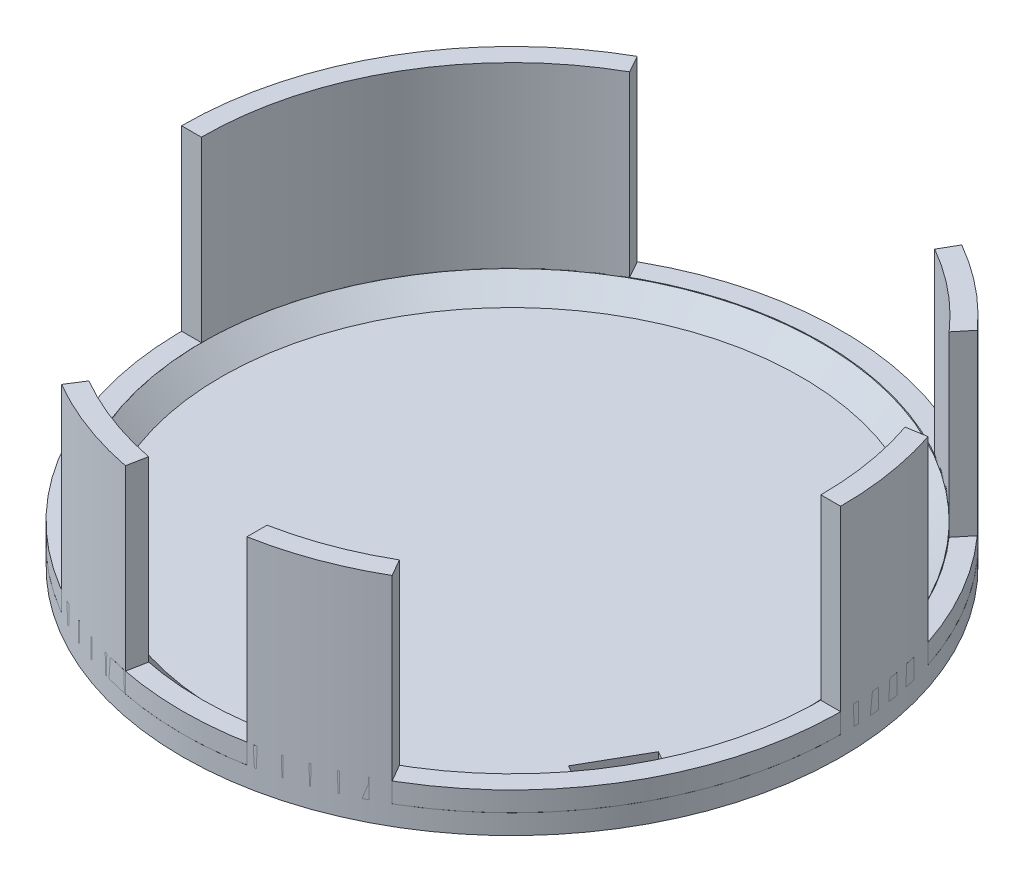
SolidWorks part; units mm, degrees
ref_plane "Front Plane" through (0, 0, 0) normal (0, 0, 1) x (1, 0, 0)
ref_plane "Top Plane" through (0, 0, 0) normal (0, 1, 0) x (1, 0, 0)
ref_plane "Right Plane" through (0, 0, 0) normal (1, 0, 0) x (0, 0, -1)
sketch "Sketch1" plane through (0, 0, 0) normal (0, 1, 0) x (1, 0, 0)
  circle A0 centre (0, 0) radius 25
extrude "Boss-Extrude1" add sketch "Sketch1" along normal blind 1.5
sketch "Sketch3" plane through (0, 1.5, 0) normal (0, 1, 0) x (1, 0, 0)
  line L0 (0, 0) -> (-16.5621, -18.7269)
  circle A0 centre (0, 0) radius 25 construction
  circle A1 centre (0, 0) radius 25
  circle A2 centre (0, 0) radius 23.5
extrude "Boss-Extrude2" add sketch "Sketch3" along normal blind 15 contours A2 A1 region at (-9.9796, 1.5, -22.1484)
sketch "Sketch4" plane through (0, 1.5, 0) normal (0, 1, 0) x (1, 0, 0)
  line L12 (12.5369, -21.6293) -> (11.7268, -20.2317)
  line L13 (-12.5582, -21.6169) -> (-11.692, -20.2518)
  line L14 (23.3845, -0.0671) -> (24.9999, -0.0671)
  line L15 (11.6192, 20.2937) -> (12.4219, 21.6955)
  line L16 (-11.4849, 20.37) -> (-12.2782, 21.7772)
  line L17 (-23.3845, -0.0671) -> (-24.9999, -0.0671)
  line L18 (4.4842, -24.5945) -> (4.4842, -22.9506)
  line L20 (-4.4866, -22.9501) -> (-4.7966, -24.5355)
  line L21 (22.1294, 7.5584) -> (23.7437, 7.8254)
  line L23 (17.5844, 15.4152) -> (18.6211, 16.681)
  circle A1 centre (0, 0) radius 23.3846
  circle A2 centre (0, 0) radius 25
  circle M13 centre (0, 0) radius 23.5
extrude "Cut-Extrude3" cut sketch "Sketch4" against normal blind 0.001 and the other way blind 15 contours L12 A2 L14 M13 | L20 A2 L18 M13 | L21 A2 L23 M13 | L15 A2 L16 M13 | L17 A2 L13 M13 region at (12.3796, 1.5, 20.8536) region at (-0.0856, 1.5, 24.1088) region at (-21.4316, 1.5, 12.3735) region at (20.8613, 1.5, -12.0676) region at (0.0818, 1.5, -24.7486)
sketch "Sketch5" plane through (0, 0, 0) normal (0, -1, 0) x (1, 0, 0)
  line L0 (0, 0) -> (18.8419, 10.7717)
  line L1 (12.6838, 21.5435) -> (25, 0)
  line L2 (18.8419, 10.7717) -> (21.7036, 12.4078)
  line L3 (18.8419, 10.7717) -> (17.6008, 12.9427)
  line L8 (17.6008, 12.9427) -> (18.4777, 13.444)
  line L9 (18.4777, 13.444) -> (20.9605, 9.1011)
  line L10 (20.9605, 9.1011) -> (19.2165, 8.1041)
  line L11 (19.2165, 8.1041) -> (16.7337, 12.447)
  line L12 (16.7337, 12.447) -> (17.6008, 12.9427)
  line L13 (55.1315, -18.0689) -> (16.7337, -26.7785)
  circle A0 centre (0, 0) radius 25 construction
extrude "Cut-Extrude4" cut sketch "Sketch5" against normal blind 5.001 contours L12 L11 L0 L1 | L9 L8 L1 L2 | L10 L9 L2 L1 | L11 L10 L1 L0 region at (17.7878, 0, 11.6094) region at (19.0292, 0, 9.4379) region at (19.9012, 0, 9.9364) region at (18.6598, 0, 12.1079)
sketch "Sketch8" plane through (0, 0, 0.0671) normal (0, 0, 1) x (1, 0, 0)
  line L0 (-23.4999, 1.5) -> (-23.4999, 3)
  line L1 (-23.4999, 1.5) -> (-23.4999, 16.5) construction
  line L2 (-23.4999, 1.5) -> (-21.9999, 1.5)
  line L3 (-23.4999, 3) -> (-21.9999, 1.5)
  line L4 (0, 0) -> (0, 7.9293)
revolve "Revolve4" add sketch "Sketch8" angle 360 about L4 region at (-22.9999, 2, 0.0671)
sketch "Sketch9" plane through (0, 1.5, 0) normal (0, 1, 0) x (1, 0, 0)
  circle A0 centre (0, 0) radius 23.5
  circle A1 centre (0, 0) radius 25
extrude "Boss-Extrude4" add sketch "Sketch9" along normal blind 1.5 separate body
sketch "Sketch10" plane through (0, 0, 0) normal (0, -1, 0) x (1, 0, 0)
  line L0 (19.2165, 8.1041) -> (20.9605, 9.1011)
  line L1 (20.9605, 9.1011) -> (18.4777, 13.444)
  line L2 (18.4777, 13.444) -> (20.9605, 9.1011) construction
  line L3 (18.4777, 13.444) -> (16.7337, 12.447)
  line L4 (16.7337, 12.447) -> (19.2165, 8.1041)
extrude "Cut-Extrude5" cut sketch "Sketch10" against normal blind 4.5
sketch "Sketch11" plane through (0, 3, 0) normal (0, 1, 0) x (1, 0, 0)
  line L0 (-23.5, 0) -> (-23.3276, -2.8414)
  line L1 (-23.3276, -2.8414) -> (-24.8274, -2.9324)
  line L2 (-24.8274, -2.9324) -> (-25, 0)
  circle A0 centre (0, 0) radius 23.5 construction
  circle A1 centre (0, 0) radius 25 construction
